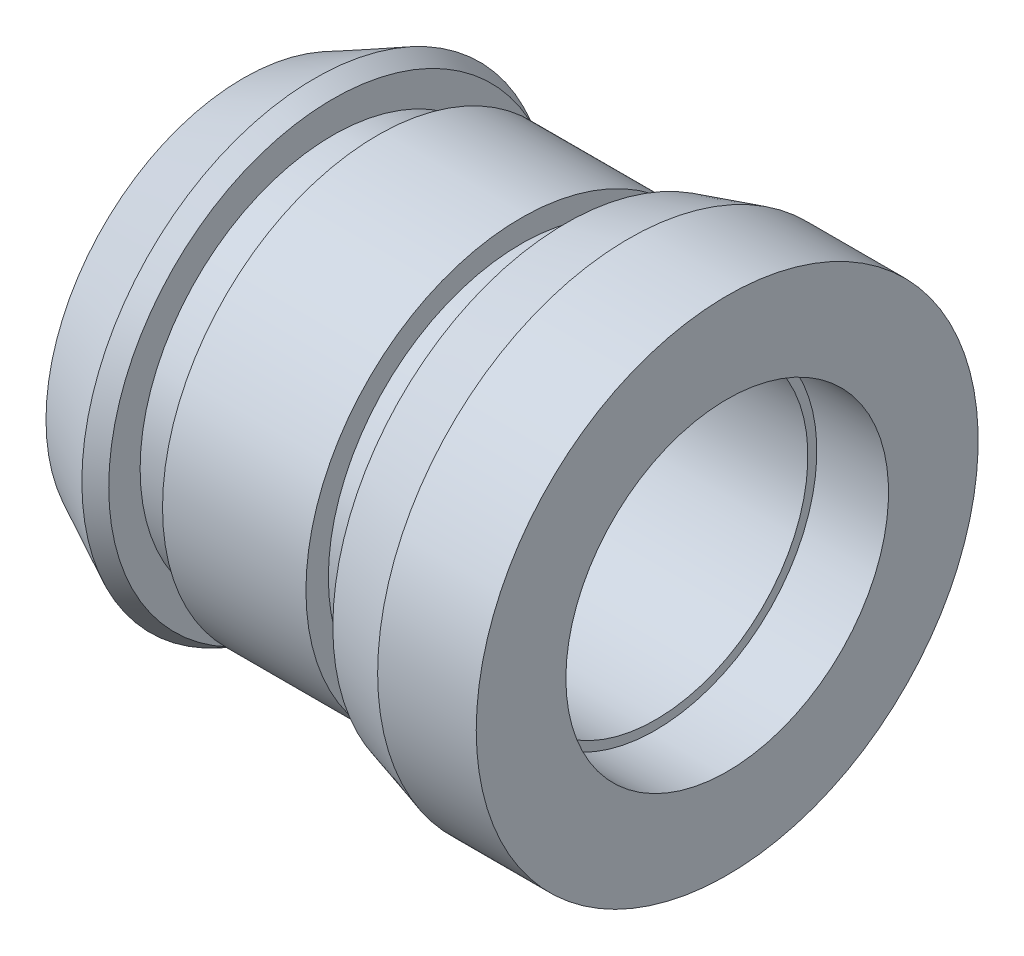
SolidWorks part; units mm, degrees
ref_plane "Front Plane" through (0, 0, 0) normal (0, 0, 1) x (1, 0, 0)
ref_plane "Top Plane" through (0, 0, 0) normal (0, 1, 0) x (1, 0, 0)
ref_plane "Right Plane" through (0, 0, 0) normal (1, 0, 0) x (0, 0, -1)
sketch "Sketch1" plane through (0, 0, 0) normal (0, 1, 0) x (1, 0, 0)
  line L0 (-96.8188, 0) -> (98.7644, 0) construction
  line L1 (-49.2125, 26.9875) -> (-49.2125, 34.925)
  line L2 (-49.2125, 34.925) -> (-36.5125, 41.275)
  line L3 (-36.5125, 41.275) -> (-33.3375, 39.6875)
  line L4 (-33.3375, 39.6875) -> (-33.3375, 34.1312)
  line L5 (-33.3375, 34.1312) -> (-25.4, 34.1313)
  line L6 (-25.4, 34.1313) -> (-25.4, 38.1)
  line L7 (-25.4, 38.1) -> (0, 38.1)
  line L8 (0, 38.1) -> (0, 34.1313)
  line L9 (0, 34.1313) -> (7.9375, 34.1313)
  line L10 (7.9375, 34.1313) -> (7.9375, 41.275)
  line L11 (7.9375, 41.275) -> (19.05, 44.45)
  line L12 (19.05, 44.45) -> (36.5125, 44.45)
  line L13 (36.5125, 44.45) -> (36.5125, 28.575)
  line L15 (-49.2125, 26.9875) -> (23.8125, 26.9875)
  line L16 (23.8125, 26.9875) -> (23.8125, 28.575)
  line L17 (23.8125, 28.575) -> (36.5125, 28.575)
  point P16 (27.2676, 26.9875)
  dimension "D1" = 12.7
  dimension "D2" = 3.175
  dimension "D3" = 7.9375
  dimension "D4" = 25.4
  dimension "D5" = 7.9375
  dimension "D6" = 11.1125
  dimension "D7" = 17.4625
  dimension "D8" = 26.9875
  dimension "D9" = 34.925
  dimension "D10" = 41.275
  dimension "D11" = 39.6875
  dimension "D12" = 34.1313
  dimension "D13" = 38.1
  dimension "D14" = 41.275
  dimension "D15" = 44.45
  dimension "D16" = 28.575
  dimension "D17" = 12.7
revolve "Revolve1" add sketch "Sketch1" angle 360 about L0
equation "\"D8@Sketch1\"=(2+1/8)/2in"
equation "\"D9@Sketch1\"=(2+3/4)/2in"
equation "\"D10@Sketch1\"=(3+1/4)/2"
equation "\"D11@Sketch1\"=(3+1/8)/2"
equation "\"D12@Sketch1\"=(2+11/16)/2"
equation "\"D14@Sketch1\"=(3+1/4)/2"
equation "\"D15@Sketch1\"=(3+1/2)/2"
equation "\"D16@Sketch1\"=(2+1/4)/2"
